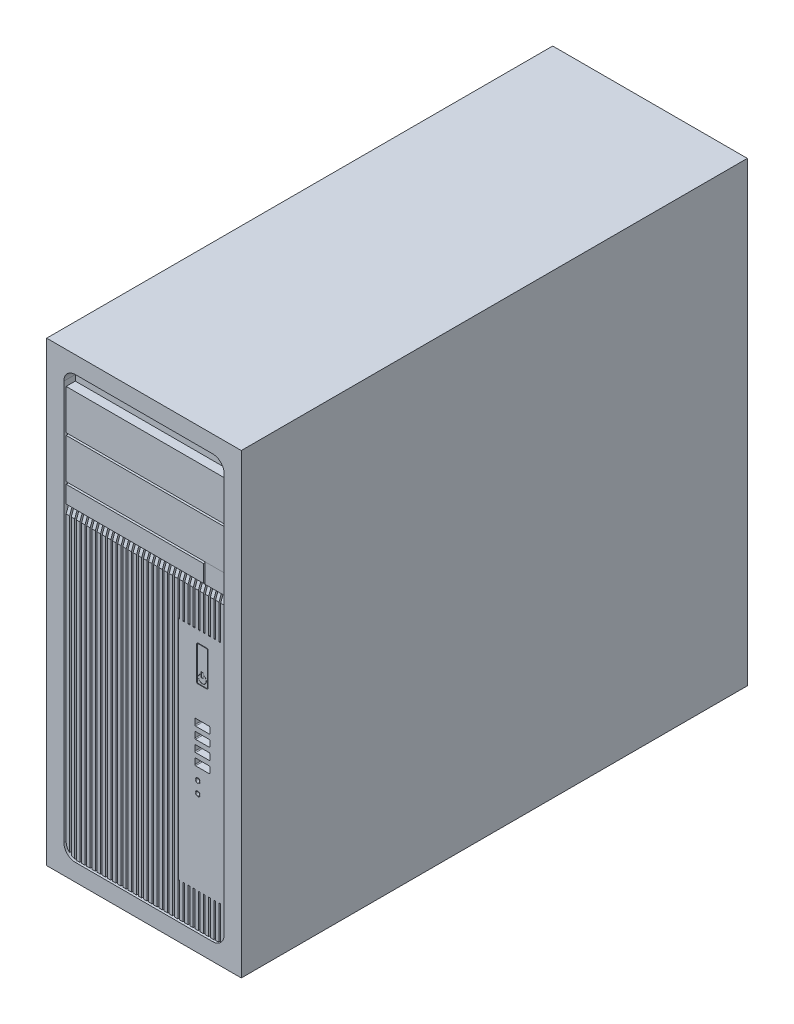
SolidWorks part; units mm, degrees
ref_plane "Front Plane" through (0, 0, 0) normal (0, 0, 1) x (1, 0, 0)
ref_plane "Top Plane" through (0, 0, 0) normal (0, 1, 0) x (1, 0, 0)
ref_plane "Right Plane" through (0, 0, 0) normal (1, 0, 0) x (0, 0, -1)
sketch "Sketch1" plane through (0, 0, 0) normal (0, 1, 0) x (1, 0, 0)
  line L1 (-85, -221) -> (85, -221)
  line L2 (-85, -221) -> (-85, 221)
  line L3 (-85, 221) -> (85, 221)
  line L4 (85, -221) -> (85, 221)
  line L5 (-85, -221) -> (85, 221) construction
  line L6 (-85, 221) -> (85, -221) construction
  point P0 (0, 0)
  dimension "D1" = 170
  dimension "D2" = 442
extrude "Boss-Extrude1" add sketch "Sketch1" along normal blind 399
sketch "Sketch2" plane through (0, 0, 221) normal (0, 0, 1) x (1, 0, 0)
  line L0 (-85, 399) -> (85, 399) construction
  line L1 (-60, 15) -> (60, 15)
  line L2 (-70, 25) -> (-70, 374)
  line L3 (-60, 384) -> (60, 384)
  line L4 (70, 25) -> (70, 374)
  line L5 (-70, 15) -> (70, 384) construction
  line L6 (-70, 384) -> (70, 15) construction
  line L7 (-85, 399) -> (-85, 0) construction
  line L8 (-85, 0) -> (85, 0) construction
  line L9 (85, 399) -> (85, 0) construction
  arc A0 (60, 15) -> (70, 25) centre (60, 25) ccw
  arc A1 (-60, 15) -> (-70, 25) centre (-60, 25) cw
  arc A2 (60, 384) -> (70, 374) centre (60, 374) cw
  arc A3 (-60, 384) -> (-70, 374) centre (-60, 374) ccw
  point P0 (0, 199.5)
  dimension "D5" = 10
  dimension "D1" = 15
  dimension "D2" = 15
  dimension "D3" = 15
  dimension "D4" = 15
extrude "Cut-Extrude1" cut sketch "Sketch2" against normal blind 10
sketch "Sketch3" plane through (0, 0, 211) normal (0, 0, 1) x (1, 0, 0)
  line L0 (70, 25) -> (70, 374) construction
  line L1 (-70, 334) -> (70, 334)
  line L2 (-70, 334) -> (-70, 369)
  line L3 (-70, 369) -> (70, 369)
  line L4 (70, 334) -> (70, 369)
  line L5 (-70, 334) -> (70, 369) construction
  line L6 (-70, 369) -> (70, 334) construction
  line L7 (60, 384) -> (-60, 384) construction
  line L8 (-70, 297) -> (70, 297)
  line L9 (-70, 297) -> (-70, 332)
  line L10 (-70, 332) -> (70, 332)
  line L11 (70, 297) -> (70, 332)
  line L12 (-70, 297) -> (70, 332) construction
  line L13 (-70, 332) -> (70, 297) construction
  point P0 (0, 351.5)
  point P7 (0, 314.5)
  dimension "D1" = 35
  dimension "D2" = 2
  dimension "D3" = 15
extrude "Boss-Extrude2" add sketch "Sketch3" along normal blind 8
sketch "Sketch4" plane through (0, 0, 211) normal (0, 0, 1) x (1, 0, 0)
  line L0 (-70, 374) -> (-70, 25) construction
  line L1 (50, 280) -> (-70, 280)
  line L2 (50, 280) -> (50, 295)
  line L3 (50, 295) -> (-70, 295)
  line L4 (-70, 280) -> (-70, 295)
  line L5 (50, 280) -> (-70, 295) construction
  line L6 (50, 295) -> (-70, 280) construction
  line L7 (-70, 297) -> (70, 297) construction
  line L8 (51.0938, 280) -> (70, 280)
  line L9 (51.0938, 280) -> (51.0938, 297)
  line L10 (51.0938, 297) -> (70, 297)
  line L11 (70, 280) -> (70, 297)
  line L12 (51.0938, 280) -> (70, 297) construction
  line L13 (51.0938, 297) -> (70, 280) construction
  point P0 (-10, 287.5)
  point P7 (60.5469, 288.5)
  dimension "D1" = 120
  dimension "D2" = 2
  dimension "D3" = 15
extrude "Boss-Extrude3" add sketch "Sketch4" along normal blind 8 separate body
sketch "Sketch5" plane through (0, 0, 211) normal (0, 0, 1) x (1, 0, 0)
  line L0 (-60, 15) -> (60, 15) construction
  line L1 (-70, 297) -> (-70, 25) construction
  line L3 (70, 25) -> (70, 297) construction
  line L4 (-60, 15) -> (60, 15)
  line L5 (-70, 278) -> (-70, 25)
  line L7 (70, 25) -> (70, 278)
  line L10 (-70, 278) -> (70, 278)
  arc A0 (-70, 25) -> (-60, 15) centre (-60, 25) ccw construction
  arc A1 (-70, 25) -> (-60, 15) centre (-60, 25) ccw
  arc A2 (60, 15) -> (70, 25) centre (60, 25) ccw construction
  arc A3 (60, 15) -> (70, 25) centre (60, 25) ccw
extrude "Boss-Extrude4" add sketch "Sketch5" along normal blind 8
chamfer "Chamfer1" distance 2 angle 70 1 edges at (0, 278, 219) first distance on face at (0, 278, 215)
sketch "Sketch6" plane through (0, 0, 219) normal (0, 0, 1) x (1, 0, 0)
  line L0 (70, 278) -> (-70, 278) construction
  line L1 (-65.5, 278) -> (-67, 278)
  line L2 (-65.5, 278) -> (-65.5, 16.6484)
  line L3 (-70, 272.505) -> (-70, 278) construction
  line L4 (-67, 278) -> (-67, 17.8586)
  arc A0 (-70, 25) -> (-60, 15) centre (-60, 25) ccw construction
  arc A1 (-67, 17.8586) -> (-65.5, 16.6484) centre (-60, 25) ccw
  dimension "D1" = 3
  dimension "D2" = 1.5
extrude "Cut-Extrude2" cut sketch "Sketch6" against normal blind 8
sketch "Sketch7" plane through (0, 0, 219) normal (0, 0, 1) x (1, 0, 0)
  line L0 (-65.5, 278) -> (70, 278) construction
  line L1 (-62.5, 278) -> (-61, 278)
  line L2 (-62.5, 278) -> (-62.5, 15)
  line L3 (-62.5, 15) -> (-61, 15)
  line L4 (-61, 278) -> (-61, 15)
  line L5 (-60, 15) -> (60, 15) construction
  line L6 (-65.5, 272.505) -> (-65.5, 278) construction
  line L7 (-58, 278) -> (-58, 15)
  line L8 (-56.5, 278) -> (-56.5, 15)
  line L9 (-58, 278) -> (-56.5, 278)
  line L10 (-58, 15) -> (-56.5, 15)
  line L11 (-53.5, 278) -> (-53.5, 15)
  line L12 (-52, 278) -> (-52, 15)
  line L13 (-53.5, 278) -> (-52, 278)
  line L14 (-53.5, 15) -> (-52, 15)
  line L15 (-49, 278) -> (-49, 15)
  line L16 (-47.5, 278) -> (-47.5, 15)
  line L17 (-49, 278) -> (-47.5, 278)
  line L18 (-49, 15) -> (-47.5, 15)
  line L19 (-44.5, 278) -> (-44.5, 15)
  line L20 (-43, 278) -> (-43, 15)
  line L21 (-44.5, 278) -> (-43, 278)
  line L22 (-44.5, 15) -> (-43, 15)
  line L23 (-40, 278) -> (-40, 15)
  line L24 (-38.5, 278) -> (-38.5, 15)
  line L25 (-40, 278) -> (-38.5, 278)
  line L26 (-40, 15) -> (-38.5, 15)
  line L27 (-35.5, 278) -> (-35.5, 15)
  line L28 (-34, 278) -> (-34, 15)
  line L29 (-35.5, 278) -> (-34, 278)
  line L30 (-35.5, 15) -> (-34, 15)
  line L31 (-31, 278) -> (-31, 15)
  line L32 (-29.5, 278) -> (-29.5, 15)
  line L33 (-31, 278) -> (-29.5, 278)
  line L34 (-31, 15) -> (-29.5, 15)
  line L35 (-26.5, 278) -> (-26.5, 15)
  line L36 (-25, 278) -> (-25, 15)
  line L37 (-26.5, 278) -> (-25, 278)
  line L38 (-26.5, 15) -> (-25, 15)
  line L39 (-22, 278) -> (-22, 15)
  line L40 (-20.5, 278) -> (-20.5, 15)
  line L41 (-22, 278) -> (-20.5, 278)
  line L42 (-22, 15) -> (-20.5, 15)
  line L43 (-17.5, 278) -> (-17.5, 15)
  line L44 (-16, 278) -> (-16, 15)
  line L45 (-17.5, 278) -> (-16, 278)
  line L46 (-17.5, 15) -> (-16, 15)
  line L47 (-13, 278) -> (-13, 15)
  line L48 (-11.5, 278) -> (-11.5, 15)
  line L49 (-13, 278) -> (-11.5, 278)
  line L50 (-13, 15) -> (-11.5, 15)
  line L51 (-8.5, 278) -> (-8.5, 15)
  line L52 (-7, 278) -> (-7, 15)
  line L53 (-8.5, 278) -> (-7, 278)
  line L54 (-8.5, 15) -> (-7, 15)
  line L55 (-4, 278) -> (-4, 15)
  line L56 (-2.5, 278) -> (-2.5, 15)
  line L57 (-4, 278) -> (-2.5, 278)
  line L58 (-4, 15) -> (-2.5, 15)
  line L59 (0.5, 278) -> (0.5, 15)
  line L60 (2, 278) -> (2, 15)
  line L61 (0.5, 278) -> (2, 278)
  line L62 (0.5, 15) -> (2, 15)
  line L63 (5, 278) -> (5, 15)
  line L64 (6.5, 278) -> (6.5, 15)
  line L65 (5, 278) -> (6.5, 278)
  line L66 (5, 15) -> (6.5, 15)
  line L67 (9.5, 278) -> (9.5, 15)
  line L68 (11, 278) -> (11, 15)
  line L69 (9.5, 278) -> (11, 278)
  line L70 (9.5, 15) -> (11, 15)
  line L71 (14, 278) -> (14, 15)
  line L72 (15.5, 278) -> (15.5, 15)
  line L73 (14, 278) -> (15.5, 278)
  line L74 (14, 15) -> (15.5, 15)
  line L75 (18.5, 278) -> (18.5, 15)
  line L76 (20, 278) -> (20, 15)
  line L77 (18.5, 278) -> (20, 278)
  line L78 (18.5, 15) -> (20, 15)
  line L79 (23, 278) -> (23, 15)
  line L80 (24.5, 278) -> (24.5, 15)
  line L81 (23, 278) -> (24.5, 278)
  line L82 (23, 15) -> (24.5, 15)
  line L83 (27.5, 278) -> (27.5, 15)
  line L84 (29, 278) -> (29, 15)
  line L85 (27.5, 278) -> (29, 278)
  line L86 (27.5, 15) -> (29, 15)
  line L87 (32, 278) -> (32, 15)
  line L88 (33.5, 278) -> (33.5, 15)
  line L89 (32, 278) -> (33.5, 278)
  line L90 (32, 15) -> (33.5, 15)
  line L91 (36.5, 278) -> (36.5, 15)
  line L92 (38, 278) -> (38, 15)
  line L93 (36.5, 278) -> (38, 278)
  line L94 (36.5, 15) -> (38, 15)
  line L95 (41, 278) -> (41, 15)
  line L96 (42.5, 278) -> (42.5, 15)
  line L97 (41, 278) -> (42.5, 278)
  line L98 (41, 15) -> (42.5, 15)
  line L99 (45.5, 278) -> (45.5, 15)
  line L100 (47, 278) -> (47, 15)
  line L101 (45.5, 278) -> (47, 278)
  line L102 (45.5, 15) -> (47, 15)
  line L103 (50, 278) -> (50, 15)
  line L104 (51.5, 278) -> (51.5, 15)
  line L105 (50, 278) -> (51.5, 278)
  line L106 (50, 15) -> (51.5, 15)
  line L107 (54.5, 278) -> (54.5, 15)
  line L108 (56, 278) -> (56, 15)
  line L109 (54.5, 278) -> (56, 278)
  line L110 (54.5, 15) -> (56, 15)
  line L111 (59, 278) -> (59, 15)
  line L112 (60.5, 278) -> (60.5, 15)
  line L113 (59, 278) -> (60.5, 278)
  line L114 (59, 15) -> (60.5, 15)
  line L115 (63.5, 278) -> (63.5, 15)
  line L116 (65, 278) -> (65, 15)
  line L117 (63.5, 278) -> (65, 278)
  line L118 (63.5, 15) -> (65, 15)
  line L119 (68, 278) -> (68, 15)
  line L120 (69.5, 278) -> (69.5, 15)
  line L121 (68, 278) -> (69.5, 278)
  line L122 (68, 15) -> (69.5, 15)
  dimension "D1" = 3
  dimension "D2" = 1.5
  dimension "D3" = 30
extrude "Cut-Extrude3" cut sketch "Sketch7" against normal blind 8
sketch "Sketch8" plane through (0, 0, 219) normal (0, 0, 1) x (1, 0, 0)
  line L0 (60, 15) -> (70, 15)
  line L1 (70, 15) -> (70, 25)
  line L3 (63.5, 15.6325) -> (63.5, 272.505)
  line L4 (63.5, 272.505) -> (60.5, 272.505)
  line L5 (60.5, 272.505) -> (60.5, 15.0125)
  line L6 (63.5, 15.6325) -> (63.5, 272.505)
  line L7 (63.5, 272.505) -> (60.5, 272.505)
  line L8 (60.5, 272.505) -> (60.5, 15.0125)
  arc A0 (60, 15) -> (70, 25) centre (60, 25) ccw construction
  arc A1 (60.5, 15.0125) -> (63.5, 15.6325) centre (60, 25) ccw
  arc A2 (60.5, 15.0125) -> (63.5, 15.6325) centre (60, 25) ccw
  arc A3 (60, 15) -> (70, 25) centre (60, 25) ccw
  arc M8 (60.5, 15.0125) -> (63.5, 15.6325) centre (60, 25) ccw
  dimension "D1" = 0
extrude "Boss-Extrude5" add sketch "Sketch8" against normal blind 8 contours A3 L0 L1 M8 region at (67.7663, 17.2337, 219)
sketch "Sketch9" plane through (0, 0, 219) normal (0, 0, 1) x (1, 0, 0)
  line L1 (70, 25) -> (70, 374) construction
  line L2 (70, 242.505) -> (28, 242.505)
  line L3 (70, 242.505) -> (70, 45)
  line L4 (70, 45) -> (28, 45)
  line L6 (28, 242.505) -> (28, 45)
  line L7 (50, 272.505) -> (47, 272.505) construction
  line L8 (38, 15) -> (41, 15) construction
  point P6 (48.5, 272.505)
  dimension "D1" = 42
  dimension "D2" = 30
  dimension "D3" = 30
extrude "Boss-Extrude6" add sketch "Sketch9" against normal blind 8
sketch "Sketch10" plane through (0, 0, 219) normal (0, 0, 1) x (1, 0, 0)
  line L0 (28, 217.005) -> (70, 217.005) construction
  line L1 (28, 242.505) -> (28, 45) construction
  line L2 (70, 25) -> (70, 272.505) construction
  line L3 (47, 242.505) -> (45.5, 242.505) construction
  line L4 (45.0572, 201.505) -> (52.9428, 201.505)
  line L5 (44.0572, 202.505) -> (44.0572, 231.505)
  line L6 (45.0572, 232.505) -> (52.9428, 232.505)
  line L7 (53.9428, 202.505) -> (53.9428, 231.505)
  line L8 (44.0572, 201.505) -> (53.9428, 232.505) construction
  line L9 (44.0572, 232.505) -> (53.9428, 201.505) construction
  line L10 (45.5572, 202.005) -> (52.4428, 202.005)
  line L11 (44.5572, 203.005) -> (44.5572, 231.005)
  line L12 (45.5572, 232.005) -> (52.4428, 232.005)
  line L13 (53.4428, 203.005) -> (53.4428, 231.005)
  line L14 (44.5572, 202.005) -> (53.4428, 232.005) construction
  line L15 (44.5572, 232.005) -> (53.4428, 202.005) construction
  arc A0 (44.0572, 202.505) -> (45.0572, 201.505) centre (45.0572, 202.505) ccw
  arc A1 (45.5572, 202.005) -> (44.5572, 203.005) centre (45.5572, 203.005) cw
  arc A2 (52.4428, 202.005) -> (53.4428, 203.005) centre (52.4428, 203.005) ccw
  arc A3 (52.9428, 201.505) -> (53.9428, 202.505) centre (52.9428, 202.505) ccw
  arc A4 (52.9428, 232.505) -> (53.9428, 231.505) centre (52.9428, 231.505) cw
  arc A5 (52.4428, 232.005) -> (53.4428, 231.005) centre (52.4428, 231.005) cw
  arc A6 (44.5572, 231.005) -> (45.5572, 232.005) centre (45.5572, 231.005) cw
  arc A7 (44.0572, 231.505) -> (45.0572, 232.505) centre (45.0572, 231.505) cw
  point P6 (49, 217.005)
  point P11 (49, 217.005)
  point P16 (46.25, 242.505)
  dimension "D5" = 1
  dimension "D1" = 0.5
  dimension "D2" = 0.5
  dimension "D3" = 30
  dimension "D4" = 10
extrude "Cut-Extrude4" cut sketch "Sketch10" against normal blind 8
sketch "Sketch11" plane through (0, 0, 219) normal (0, 0, 1) x (1, 0, 0)
  line L0 (44.5572, 207.005) -> (53.4428, 207.005)
  line L1 (53.4428, 203.005) -> (53.4428, 231.005) construction
  line L2 (44.5572, 231.005) -> (44.5572, 203.005) construction
  line L4 (48, 207.805) -> (50, 207.805)
  line L5 (48, 207.805) -> (48, 212.205)
  line L6 (48, 212.205) -> (50, 212.205)
  line L7 (50, 207.805) -> (50, 212.205)
  line L8 (48, 207.805) -> (50, 212.205) construction
  line L9 (48, 212.205) -> (50, 207.805) construction
  line L10 (48.2, 208.005) -> (49.8, 208.005)
  line L11 (48.2, 208.005) -> (48.2, 212.005)
  line L12 (48.2, 212.005) -> (49.8, 212.005)
  line L13 (49.8, 208.005) -> (49.8, 212.005)
  line L14 (48.2, 208.005) -> (49.8, 212.005) construction
  line L15 (48.2, 212.005) -> (49.8, 208.005) construction
  line L16 (48, 212.205) -> (48.2, 212.205)
  line L17 (48, 212.205) -> (48, 212.005)
  line L18 (48, 212.005) -> (48.2, 212.005)
  line L19 (48.2, 212.205) -> (48.2, 212.005)
  line L21 (47.4672, 210.1516) -> (47.4672, 209.9275)
  line L22 (49, 210.005) -> (49, 209.2855) construction
  line L23 (50.5328, 210.1516) -> (50.5328, 209.9275)
  line L24 (45.5572, 202.005) -> (52.4428, 202.005) construction
  arc A0 (47.4672, 210.1516) -> (50.5328, 210.1516) centre (49, 207.005) ccw
  arc A1 (47.4672, 209.9275) -> (50.5328, 209.9275) centre (49, 207.005) ccw
  arc A4 (48.7712, 210.5771) -> (48.7409, 210.5751) centre (49, 207.005) ccw
  arc A5 (48.8519, 210.3752) -> (48.8322, 210.3743) centre (49, 207.005) ccw
  arc A6 (49.1678, 210.3743) -> (49.1481, 210.3752) centre (49, 207.005) ccw
  arc A7 (49.2591, 210.5751) -> (49.2288, 210.5771) centre (49, 207.005) ccw
  point P5 (49, 207.005)
  point P10 (49, 210.005)
  point P15 (49, 210.005)
  dimension "D1" = 0.2
  dimension "D4" = 7
  dimension "D2" = 0.2
  dimension "D3" = 4
  dimension "D5" = 3
  dimension "D6" = 5
  dimension "D7" = 2
extrude "Cut-Extrude5" cut sketch "Sketch11" against normal blind 1 contours L6 L19 L12 L13 L10 L11 L18 L5 L4 L7 | A1 L0 A0 L23 | L19 L6 L5 L18 | A1 L21 A0 L0 | A1 L0 A0 region at (46.0637, 208.8408, 219) region at (45.6, 206.9268, 219) region at (52.4, 207.0422, 219) region at (48.0483, 209.905, 219) region at (48.1, 212.105, 219)
sketch "Sketch13" plane through (0, 0, 219) normal (0, 0, 1) x (1, 0, 0)
  line L1 (43.11, 168.545) -> (54.89, 168.545)
  line L2 (42.35, 169.305) -> (42.35, 173.705)
  line L3 (43.11, 174.465) -> (54.89, 174.465)
  line L4 (55.65, 169.305) -> (55.65, 173.705)
  line L5 (42.35, 168.545) -> (55.65, 174.465) construction
  line L6 (42.35, 174.465) -> (55.65, 168.545) construction
  line L8 (49, 171.505) -> (28, 171.505) construction
  line L9 (28, 242.505) -> (28, 45) construction
  line L10 (49, 171.505) -> (70, 171.505) construction
  line L11 (70, 25) -> (70, 272.505) construction
  line L12 (42.35, 158.545) -> (42.35, 164.465)
  line L13 (42.35, 164.465) -> (55.65, 164.465)
  line L14 (42.35, 158.545) -> (55.65, 158.545)
  line L15 (55.65, 158.545) -> (55.65, 164.465)
  line L16 (42.35, 148.545) -> (42.35, 154.465)
  line L17 (42.35, 154.465) -> (55.65, 154.465)
  line L18 (42.35, 148.545) -> (55.65, 148.545)
  line L19 (55.65, 148.545) -> (55.65, 154.465)
  line L20 (42.35, 138.545) -> (42.35, 144.465)
  line L21 (42.35, 144.465) -> (55.65, 144.465)
  line L22 (42.35, 138.545) -> (55.65, 138.545)
  line L23 (55.65, 138.545) -> (55.65, 144.465)
  line L24 (45.0572, 201.505) -> (52.9428, 201.505) construction
  arc A0 (54.89, 174.465) -> (55.65, 173.705) centre (54.89, 173.705) cw
  arc A1 (54.89, 168.545) -> (55.65, 169.305) centre (54.89, 169.305) ccw
  arc A2 (43.11, 168.545) -> (42.35, 169.305) centre (43.11, 169.305) cw
  arc A3 (42.35, 173.705) -> (43.11, 174.465) centre (43.11, 173.705) cw
  arc A4 (43.11, 158.545) -> (42.35, 159.305) centre (43.11, 159.305) cw
  arc A5 (42.35, 163.705) -> (43.11, 164.465) centre (43.11, 163.705) cw
  arc A6 (54.89, 164.465) -> (55.65, 163.705) centre (54.89, 163.705) cw
  arc A7 (54.89, 158.545) -> (55.65, 159.305) centre (54.89, 159.305) ccw
  arc A8 (43.11, 148.545) -> (42.35, 149.305) centre (43.11, 149.305) cw
  arc A9 (42.35, 153.705) -> (43.11, 154.465) centre (43.11, 153.705) cw
  arc A10 (54.89, 154.465) -> (55.65, 153.705) centre (54.89, 153.705) cw
  arc A11 (54.89, 148.545) -> (55.65, 149.305) centre (54.89, 149.305) ccw
  arc A12 (43.11, 138.545) -> (42.35, 139.305) centre (43.11, 139.305) cw
  arc A13 (42.35, 143.705) -> (43.11, 144.465) centre (43.11, 143.705) cw
  arc A14 (54.89, 144.465) -> (55.65, 143.705) centre (54.89, 143.705) cw
  arc A15 (54.89, 138.545) -> (55.65, 139.305) centre (54.89, 139.305) ccw
  point P0 (49, 171.505)
  dimension "D5" = 0.76
  dimension "D1" = 13.3
  dimension "D2" = 5.92
  dimension "D4" = 30
  dimension "D3" = 4
  dimension "D6" = 4
extrude "Cut-Extrude6" cut sketch "Sketch13" against normal blind 8 contours L14 A7 L15 A6 L13 A5 L12 A4 | A3 L2 A2 L1 A1 L4 A0 L3 | L18 A11 L19 A10 L17 A9 L16 A8 | L22 A15 L23 A14 L21 A13 L20 A12 region at (49, 171.505, 219) region at (49, 161.505, 219) region at (49, 151.505, 219) region at (49, 141.505, 219)
sketch "Sketch14" plane through (0, 0, 219) normal (0, 0, 1) x (1, 0, 0)
  circle A0 centre (44.9801, 128.3306) radius 1.9
  circle A1 centre (44.9801, 118.3306) radius 1.9
  circle A2 centre (44.9801, 128.3306) radius 2.1
  circle A3 centre (44.9801, 118.3306) radius 2.1
  circle A4 centre (44.9801, 128.3306) radius 1.7
  circle A5 centre (44.9801, 118.3306) radius 1.7
  dimension "D1" = 3.8
  dimension "D2" = 10
  dimension "D3" = 0.2
  dimension "D4" = 0.2
  dimension "D5" = 0.2
extrude "Cut-Extrude7" cut sketch "Sketch14" against normal blind 8 contours A2 A0 | A4 | A5 | A3 A1 region at (42.9395, 128.3306, 219) region at (42.9395, 118.3306, 219) region at (44.9801, 128.3306, 219) region at (44.9801, 118.3306, 219)
sketch "Sketch16" plane through (0, 0, 0) normal (0, -1, 0) x (1, 0, 0)
